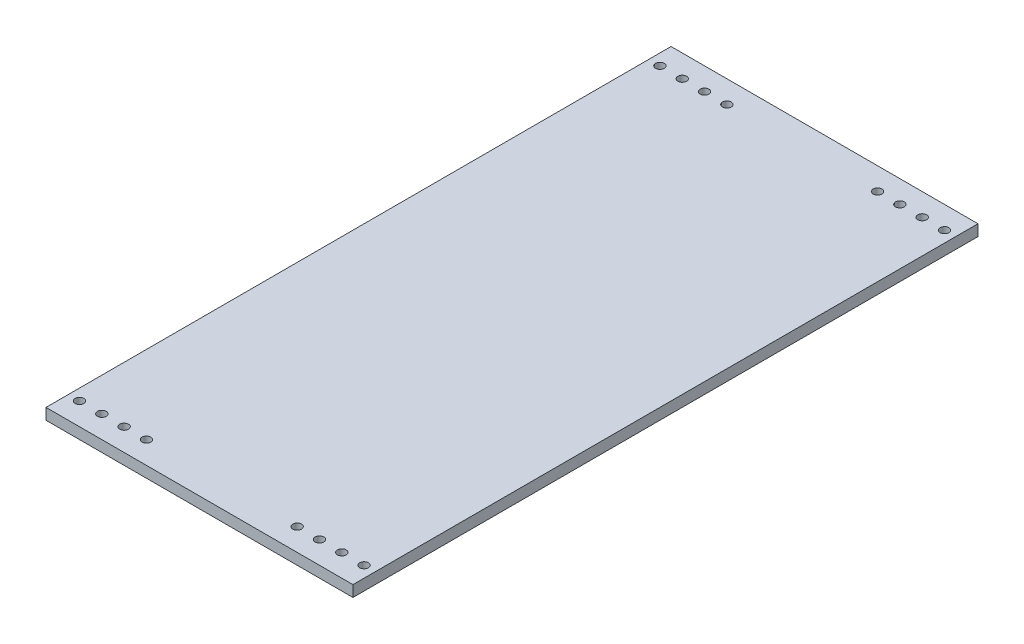
SolidWorks part; units mm, degrees
material "PC High Viscosity"
ref_plane "Front Plane" through (0, 0, 0) normal (0, 0, 1) x (1, 0, 0)
ref_plane "Top Plane" through (0, 0, 0) normal (0, 1, 0) x (1, 0, 0)
ref_plane "Right Plane" through (0, 0, 0) normal (1, 0, 0) x (0, 0, -1)
sketch "Sketch1" plane through (0, 0, 0) normal (0, 1, 0) x (1, 0, 0)
  line L1 (-87.3125, -177.8) -> (87.3125, -177.8)
  line L2 (-87.3125, -177.8) -> (-87.3125, 177.8)
  line L3 (-87.3125, 177.8) -> (87.3125, 177.8)
  line L4 (87.3125, -177.8) -> (87.3125, 177.8)
  line L5 (-87.3125, -177.8) -> (87.3125, 177.8) construction
  line L6 (-87.3125, 177.8) -> (87.3125, -177.8) construction
  point P0 (0, 0)
  dimension "D1" = 174.625
  dimension "D2" = 355.6
extrude "Boss-Extrude1" add sketch "Sketch1" along normal blind 6.35
sketch "Sketch2" plane through (0, 6.35, 0) normal (0, 1, 0) x (1, 0, 0)
  line L0 (87.3125, -177.8) -> (87.3125, 177.8) construction
  line L1 (-87.3125, -177.8) -> (87.3125, -177.8) construction
  line L2 (-87.3125, 0) -> (87.3125, 0) construction
  line L3 (-87.3125, 177.8) -> (-87.3125, -177.8) construction
  line L4 (0, 177.8) -> (0, -177.8) construction
  line L5 (87.3125, 177.8) -> (-87.3125, 177.8) construction
  circle A0 centre (80.9625, -165.1) radius 2.4892
  circle A1 centre (68.2625, -165.1) radius 2.4892
  circle A2 centre (55.5625, -165.1) radius 2.4892
  circle A3 centre (42.8625, -165.1) radius 2.4892
  circle A4 centre (80.9625, 165.1) radius 2.4892
  circle A5 centre (68.2625, 165.1) radius 2.4892
  circle A6 centre (55.5625, 165.1) radius 2.4892
  circle A7 centre (42.8625, 165.1) radius 2.4892
  circle A8 centre (80.9625, 165.1) radius 2.4892
  circle A9 centre (68.2625, 165.1) radius 2.4892
  circle A10 centre (55.5625, 165.1) radius 2.4892
  circle A11 centre (42.8625, 165.1) radius 2.4892
  circle A12 centre (-80.9625, -165.1) radius 2.4892
  circle A13 centre (-68.2625, -165.1) radius 2.4892
  circle A14 centre (-55.5625, -165.1) radius 2.4892
  circle A15 centre (-42.8625, -165.1) radius 2.4892
  circle A16 centre (-80.9625, 165.1) radius 2.4892
  circle A17 centre (-68.2625, 165.1) radius 2.4892
  circle A18 centre (-55.5625, 165.1) radius 2.4892
  circle A19 centre (-42.8625, 165.1) radius 2.4892
  dimension "D1" = 4.9784
  dimension "D2" = 6.35
  dimension "D3" = 12.7
  dimension "D5" = 12.7
  dimension "D4" = 4
extrude "Cut-Extrude2" cut sketch "Sketch2" against normal through all contours A15 | A14 | A13 | A12 | A4 | A5 | A6 | A7 | A16 | A17 | A18 | A19 | A3 | A2 | A1 | A0 region at (80.9625, 6.35, -165.1) region at (68.2625, 6.35, -165.1) region at (55.5625, 6.35, -165.1) region at (42.8625, 6.35, -165.1) region at (-80.9625, 6.35, 165.1) region at (-68.2625, 6.35, 165.1) region at (-55.5625, 6.35, 165.1) region at (-42.8625, 6.35, 165.1) region at (-80.9625, 6.35, -165.1) region at (-68.2625, 6.35, -165.1) region at (-55.5625, 6.35, -165.1) region at (-42.8625, 6.35, -165.1)
